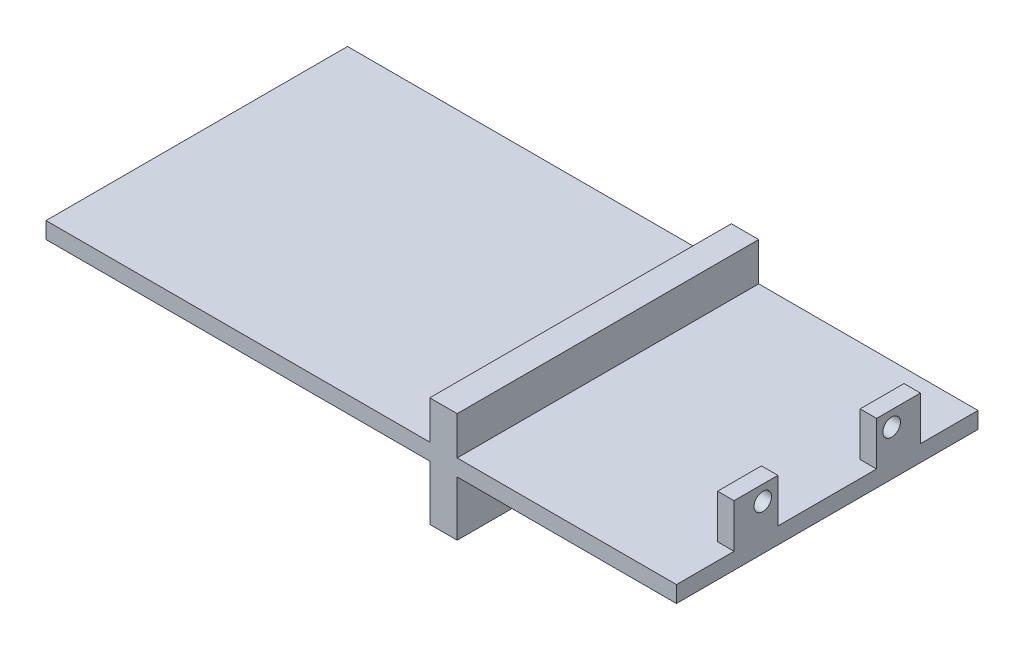
SolidWorks part; units mm, degrees
material "ABS"
ref_plane "Front Plane" through (0, 0, 0) normal (0, 0, 1) x (1, 0, 0)
ref_plane "Top Plane" through (0, 0, 0) normal (0, 1, 0) x (1, 0, 0)
ref_plane "Right Plane" through (0, 0, 0) normal (1, 0, 0) x (0, 0, -1)
sketch "Sketch2" plane through (0, 0, 0) normal (0, 1, 0) x (1, 0, 0)
  line L1 (-30.5455, 36.5455) -> (39.4545, 36.5455)
  line L2 (-30.5455, 36.5455) -> (-30.5455, -18.4545)
  line L3 (-30.5455, -18.4545) -> (39.4545, -18.4545)
  line L4 (39.4545, 36.5455) -> (39.4545, -18.4545)
  line L5 (39.4545, 36.5455) -> (44.4545, 36.5455)
  line L6 (39.4545, 36.5455) -> (39.4545, -18.4545)
  line L7 (39.4545, -18.4545) -> (44.4545, -18.4545)
  line L8 (44.4545, 36.5455) -> (44.4545, -18.4545)
  dimension "D1" = 70
  dimension "D2" = 55
  dimension "D3" = 5
sketch "Sketch5" plane through (0, 0, 0) normal (0, 1, 0) x (1, 0, 0)
  line L1 (39.4545, 36.5455) -> (44.4545, 36.5455)
  line L2 (39.4545, 36.5455) -> (39.4545, -18.4545)
  line L3 (39.4545, -18.4545) -> (44.4545, -18.4545)
  line L4 (44.4545, 36.5455) -> (44.4545, -18.4545)
extrude "Boss-Extrude3" add sketch "Sketch2" along normal blind 3 contours L4 L1 L2 L3 region at (4.4545, 0, -9.0455)
extrude "Boss-Extrude4" add sketch "Sketch5" along normal blind 10 and the other way blind 10
sketch "Sketch6" plane through (0, 0, 0) normal (0, 1, 0) x (1, 0, 0)
  line L1 (44.4545, 36.5455) -> (84.4545, 36.5455)
  line L2 (44.4545, 36.5455) -> (44.4545, -18.4545)
  line L3 (44.4545, -18.4545) -> (84.4545, -18.4545)
  line L4 (84.4545, 36.5455) -> (84.4545, -18.4545)
  dimension "D1" = 40
extrude "Boss-Extrude5" add sketch "Sketch6" along normal blind 3
sketch "Sketch8" plane through (0, 0, 0) normal (0, 1, 0) x (1, 0, 0)
  line L0 (84.4545, -18.4545) -> (84.4545, 36.5455) construction
  line L1 (84.4545, 26.0455) -> (81.4545, 26.0455)
  line L2 (84.4545, 26.0455) -> (84.4545, 18.0455)
  line L3 (84.4545, 18.0455) -> (81.4545, 18.0455)
  line L4 (81.4545, 26.0455) -> (81.4545, 18.0455)
  line L5 (44.4545, -18.4545) -> (84.4545, -18.4545) construction
  line L6 (84.4545, 0.0455) -> (81.4545, 0.0455)
  line L7 (84.4545, 0.0455) -> (84.4545, -7.9545)
  line L8 (84.4545, -7.9545) -> (81.4545, -7.9545)
  line L9 (81.4545, 0.0455) -> (81.4545, -7.9545)
  dimension "D1" = 8
  dimension "D2" = 8
  dimension "D3" = 18
  dimension "D4" = 10.5
  dimension "D5" = 3
  dimension "D6" = 3
extrude "Boss-Extrude6" add sketch "Sketch8" along normal blind 11
sketch "Sketch9" plane through (84.4545, 0, 0) normal (1, 0, 0) x (0, 0, -1)
  line L0 (0.0455, 11) -> (0.0455, 3) construction
  line L1 (-7.9545, 11) -> (0.0455, 11) construction
  line L2 (18.0455, 11) -> (18.0455, 3) construction
  line L3 (18.0455, 11) -> (26.0455, 11) construction
  line L4 (-7.9545, 3) -> (0.0455, 3) construction
  circle A0 centre (-2.7045, 8.25) radius 1.6
  circle A1 centre (20.7955, 8.25) radius 1.6
  point P2 (0, 0)
  point P9 (20.4777, 8.25)
  dimension "D1" = 2.75
  dimension "D3" = 2.75
  dimension "D2" = 2.75
  dimension "D4" = 2.75
extrude "Cut-Extrude1" cut sketch "Sketch9" against normal blind 11
